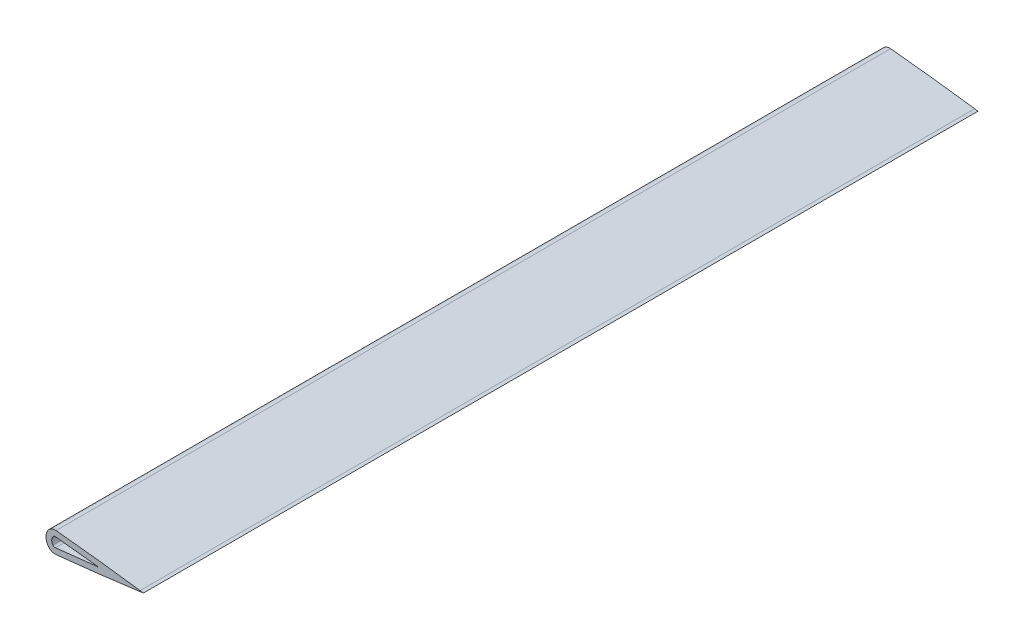
SolidWorks part; units mm, degrees
material "ABS"
ref_plane "Front Plane" through (0, 0, 0) normal (0, 0, 1) x (1, 0, 0)
ref_plane "Top Plane" through (0, 0, 0) normal (0, 1, 0) x (1, 0, 0)
ref_plane "Right Plane" through (0, 0, 0) normal (1, 0, 0) x (0, 0, -1)
sketch "Sketch2" plane through (0, 0, 125) normal (0, 0, 1) x (1, 0, 0)
  line L6 (72.8985, 242.6983) -> (74.0667, 242.8596)
  line L7 (74.0667, 242.8596) -> (72.8985, 243.0209)
  arc A0 (42.4402, 246.6168) -> (42.4403, 239.1025) centre (44.0667, 242.8596) ccw
  spline S4 degree 3 poles (72.8985, 243.0209) (68.2268, 243.666) (58.8702, 244.8607) (48.7077, 245.9849) (43.2279, 246.5384) (42.4402, 246.6168) knots 0.003074 0.003074 0.003074 0.003074 0.064763 0.126452 0.136805 0.136805 0.136805 0.136805
  spline S5 degree 3 poles (42.4403, 239.1025) (43.2279, 239.1809) (48.7077, 239.7343) (58.8701, 240.8588) (68.2267, 242.0534) (72.8985, 242.6983) knots 0.856366 0.856366 0.856366 0.856366 0.866719 0.928408 0.990097 0.990097 0.990097 0.990097
extrude "Boss-Extrude1" add sketch "Sketch2" along normal mid plane 292
fillet "Fillet1" radius 3 2 edges at (42.4403, 239.1025, 125) (42.4402, 246.6168, 125)
sketch "Sketch5" plane through (0, 0, 271) normal (0, 0, 1) x (1, 0, 0)
  arc A6 (42.4055, 244.1346) -> (42.4055, 241.5847) centre (44.0667, 242.8596) ccw
  arc A7 (42.4055, 241.5847) -> (43.2991, 241.1985) centre (43.1988, 242.1935) ccw
  arc A8 (43.2991, 244.5207) -> (42.4055, 244.1346) centre (43.1988, 243.5257) ccw
  arc A9 (42.4055, 244.1346) -> (42.4055, 241.5847) centre (44.0667, 242.8596) ccw
  arc A10 (42.4055, 241.5847) -> (43.2991, 241.1985) centre (43.1988, 242.1935) ccw
  arc A11 (43.2991, 244.5207) -> (42.4055, 244.1346) centre (43.1988, 243.5257) ccw
  spline S4 degree 3 poles (2861.3701, -2544.8866) (-5145.0627, 4423.3205) (2629.1087, -3992.6803) (320.6233, 3941.4993) knots -200.875743 -200.875743 -200.875743 -200.875743 118.902758 118.902758 118.902758 118.902758 only from (43.2991, 241.1985) to (58.4244, 242.8597)
  spline S5 degree 3 poles (1185.4758, -3407.8825) (1000.8046, 4063.6158) (-1881.0107, -3339.9525) (-1651.9487, 2926.2625) knots -110.814992 -110.814992 -110.814992 -110.814992 169.109579 169.109579 169.109579 169.109579 only from (58.4244, 242.8597) to (43.2991, 244.5207)
  spline S6 degree 3 poles (43.2991, 241.1985) (48.3457, 241.7074) (53.3878, 242.2608) (58.4244, 242.8597) knots 0 0 0 0 1 1 1 1
  spline S7 degree 3 poles (58.4244, 242.8597) (53.3877, 243.4586) (48.3458, 244.0118) (43.2991, 244.5207) knots 0 0 0 0 1 1 1 1
  dimension "D1" = 2
extrude "Cut-Extrude2" cut sketch "Sketch5" against normal up to surface (292 mm away) up to face at (55.3363, 242.3611, -21)
sketch "Sketch3" plane through (0, 242.8596, 0) normal (0, -1, 0) x (1, 0, 0)
  line L0 (74.0667, 125) -> (21.6985, 125) construction
  line L1 (24.3034, 205) -> (59.3034, 205)
  line L2 (24.3034, 205) -> (24.3034, 185)
  line L3 (24.3034, 185) -> (59.3034, 185)
  line L4 (59.3034, 205) -> (59.3034, 185)
  line L5 (74.0667, 271) -> (74.0667, -21) construction
  line L6 (59.3034, 45) -> (59.3034, 65)
  line L7 (24.3034, 65) -> (59.3034, 65)
  line L8 (24.3034, 45) -> (24.3034, 65)
  line L9 (24.3034, 45) -> (59.3034, 45)
extrude "Cut-Extrude1" cut sketch "Sketch3" along normal through all
fillet "Fillet2" radius 3 4 edges at (59.3034, 241.905, 185) (59.3034, 241.905, 205) (59.3034, 241.905, 65) (59.3034, 241.905, 45)
